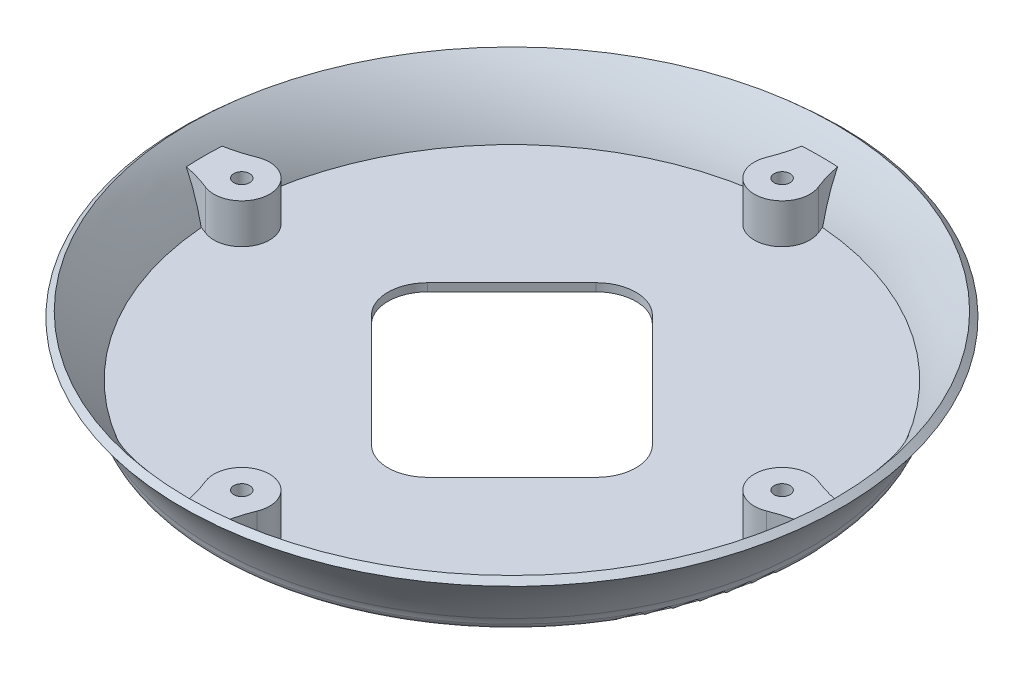
SolidWorks part; units mm, degrees
ref_plane "Front Plane" through (0, 0, 0) normal (0, 0, 1) x (1, 0, 0)
ref_plane "Top Plane" through (0, 0, 0) normal (0, 1, 0) x (1, 0, 0)
ref_plane "Right Plane" through (0, 0, 0) normal (1, 0, 0) x (0, 0, -1)
sketch "Sketch1" plane through (0, 0, 0) normal (0, 0, 1) x (1, 0, 0)
  line L0 (-25.5, 30) -> (-25.5, 0) construction
  line L1 (-25.5, 0) -> (-70, 0) construction
  line L2 (0, 0) -> (0, 35) construction
  line L3 (-70, 0) -> (-81.459, 30) construction
  arc A0 (-70, 0) -> (-81.459, 30) centre (-115, 0) ccw
  dimension "D1" = 35
  dimension "D5" = 45
  dimension "D2" = 30
  dimension "D3" = 70
  dimension "D4" = 25.5
  dimension "D7" = 30
revolve "Revolve-Thin1" add sketch "Sketch1" angle 360 about L2 wall 2
ref_plane "Plane1" through (0, 25, 0) normal (0, -1, 0) x (-1, 0, 0)
sketch "Sketch2" plane through (0, 25, 0) normal (0, -1, 0) x (-1, 0, 0)
  line L0 (-68, 0) -> (-81.459, 0) construction
  line L1 (-81.459, -4) -> (-81.459, 4)
  line L2 (-4, 86.7157) -> (4, 86.7157)
  line L3 (0, 68) -> (0, 86.7157) construction
  line L4 (86.7157, 4) -> (86.7157, -4)
  line L5 (68, 0) -> (81.3633, 0) construction
  line L6 (4, -86.7157) -> (-4, -86.7157)
  line L7 (0, -68) -> (0, -86.7157) construction
  circle A0 centre (-68, 0) radius 2
  arc A1 (-70.6057, -6.4969) -> (-70.6057, 6.4969) centre (-68, 0) ccw
  circle A2 centre (0, 0) radius 81.459 construction
  arc A3 (-81.3604, 4.0071) -> (-81.3604, -4.0071) centre (0, 0) ccw
  arc A4 (-70.6057, 6.4969) -> (-81.459, 4) centre (-84.0066, 39.9097) cw
  arc A5 (-70.6057, -6.4969) -> (-81.459, -4) centre (-84.0066, -39.9097) ccw
  arc A6 (6.4953, 70.6098) -> (4, 86.7157) centre (39.8998, 84.0314) cw
  arc A7 (-6.4953, 70.6098) -> (6.4953, 70.6098) centre (0, 68) ccw
  circle A8 centre (0, 68) radius 2
  arc A9 (-6.4953, 70.6098) -> (-4, 86.7157) centre (-39.8998, 84.0314) ccw
  arc A10 (70.6098, -6.4953) -> (86.7157, -4) centre (84.0314, -39.8998) cw
  arc A11 (70.6098, 6.4953) -> (70.6098, -6.4953) centre (68, 0) ccw
  circle A12 centre (68, 0) radius 2
  arc A13 (70.6098, 6.4953) -> (86.7157, 4) centre (84.0314, 39.8998) ccw
  arc A14 (-6.4953, -70.6098) -> (-4, -86.7157) centre (-39.8998, -84.0314) cw
  arc A15 (6.4953, -70.6098) -> (-6.4953, -70.6098) centre (0, -68) ccw
  circle A16 centre (0, -68) radius 2
  arc A17 (6.4953, -70.6098) -> (4, -86.7157) centre (39.8998, -84.0314) ccw
  point P10 (-81.459, 0)
  dimension "D1" = 4
  dimension "D2" = 14
  dimension "D4" = 36
  dimension "D5" = 68
  dimension "D3" = 8
  dimension "D6" = 68
  dimension "D7" = 68
  dimension "D8" = 68
extrude "Boss-Extrude1" add sketch "Sketch2" along normal up to surface (25 mm away) contours A17 A15 A14 L6 A16 | A13 A11 A10 L4 A12 | A9 A7 A6 L2 A8 | A5 A1 A4 A3 A0 region at (71.0314, 25, 0) region at (0, 25, -73.2096) region at (-73.2096, 25, 0) region at (0, 25, 73.2096) up to face at (0, 0, -72)
sketch "Sketch3" plane through (0, 0, 0) normal (0, 0, 1) x (1, 0, 0)
  line L0 (-72, 0) -> (-99.1272, 0)
  line L1 (-99.1272, 0) -> (-99.1272, 28.6667)
  line L3 (-99.1272, 28.6667) -> (-82.9497, 28.6667)
  arc A0 (-70, 0) -> (-81.459, 30) centre (-115, 0) ccw construction
  arc A4 (-72, 0) -> (-82.9497, 28.6667) centre (-115, 0) ccw
  arc A5 (-72, 0) -> (-82.9497, 28.6667) centre (-115, 0) ccw
  dimension "D1" = 2
revolve "Cut-Revolve1" cut sketch "Sketch3" angle 360 about L2
sketch "Sketch4" plane through (0, 0, 0) normal (1, 0, 0) x (0, 0, -1)
  line L0 (81.459, 30) -> (-81.459, 30) construction
  line L1 (-90, 0) -> (90, 0)
  line L2 (-90, 0) -> (-90, 15)
  line L3 (-90, 15) -> (90, 15)
  line L4 (90, 0) -> (90, 15)
  line L5 (-72, 0) -> (72, 0) construction
  point P8 (0, 0)
  dimension "D1" = 15
  dimension "D2" = 180
extrude "Cut-Extrude1" cut sketch "Sketch4" against normal up to surface and the other way up to surface up to face at (0, 0, -72) other way up to face at (0, 0, -72)
sketch "Sketch5" plane through (0, 15, 0) normal (0, -1, 0) x (1, 0, 0)
  circle A0 centre (0, 0) radius 74.7011 construction
  circle A1 centre (0, 0) radius 74.7011
  circle A2 centre (68, 0) radius 2 construction
  circle A3 centre (68, 0) radius 2
  circle A4 centre (0, 68) radius 2 construction
  circle A5 centre (-68, 0) radius 2 construction
  circle A6 centre (0, -68) radius 2 construction
  circle A7 centre (0, 68) radius 2
  circle A8 centre (-68, 0) radius 2
  circle A9 centre (0, -68) radius 2
extrude "Boss-Extrude2" add sketch "Sketch5" along normal blind 2
sketch "Sketch6" plane through (0, 13, 0) normal (0, -1, 0) x (1, 0, 0)
  circle A2 centre (0, 68) radius 5
  circle A3 centre (0, 68) radius 5
  circle A5 centre (68, 0) radius 5
  circle A6 centre (68, 0) radius 5
  circle A8 centre (0, -68) radius 5
  circle A9 centre (0, -68) radius 5
  circle A11 centre (-68, 0) radius 5
  circle A12 centre (-68, 0) radius 5
  dimension "D1" = 3
  dimension "D2" = 3
  dimension "D3" = 3
  dimension "D4" = 3
extrude "Cut-Extrude2" cut sketch "Sketch6" against normal blind 8
fillet "Fillet1" radius 2 1 edges at (0, 13, -74.7011)
fillet "Fillet2" radius 10 1 edges at (0, 15, -74.7011)
sketch "Sketch7" plane through (0, 15, 0) normal (0, 1, 0) x (1, 0, 0)
  line L0 (0, 68) -> (-68, 0) construction
  line L1 (10.6066, -31.8198) -> (31.8198, -10.6066)
  line L2 (-3.5355, -31.8198) -> (-31.8198, -3.5355)
  line L3 (-31.8198, 10.6066) -> (-10.6066, 31.8198)
  line L4 (31.8198, 3.5355) -> (3.5355, 31.8198)
  line L5 (3.5355, -38.8909) -> (-3.5355, 38.8909) construction
  line L6 (-38.8909, 3.5355) -> (38.8909, -3.5355) construction
  line L7 (-34, 34) -> (30.6669, -30.6669) construction
  arc A0 (10.6066, -31.8198) -> (-3.5355, -31.8198) centre (3.5355, -24.7487) cw
  arc A1 (31.8198, -10.6066) -> (31.8198, 3.5355) centre (24.7487, -3.5355) ccw
  arc A2 (-10.6066, 31.8198) -> (3.5355, 31.8198) centre (-3.5355, 24.7487) cw
  arc A3 (-31.8198, -3.5355) -> (-31.8198, 10.6066) centre (-24.7487, 3.5355) cw
  point P0 (0, 0)
  point P24 (-21.2132, 21.2132)
  dimension "D3" = 10
  dimension "D1" = 60
  dimension "D2" = 50
extrude "Cut-Extrude3" cut sketch "Sketch7" against normal up to next
